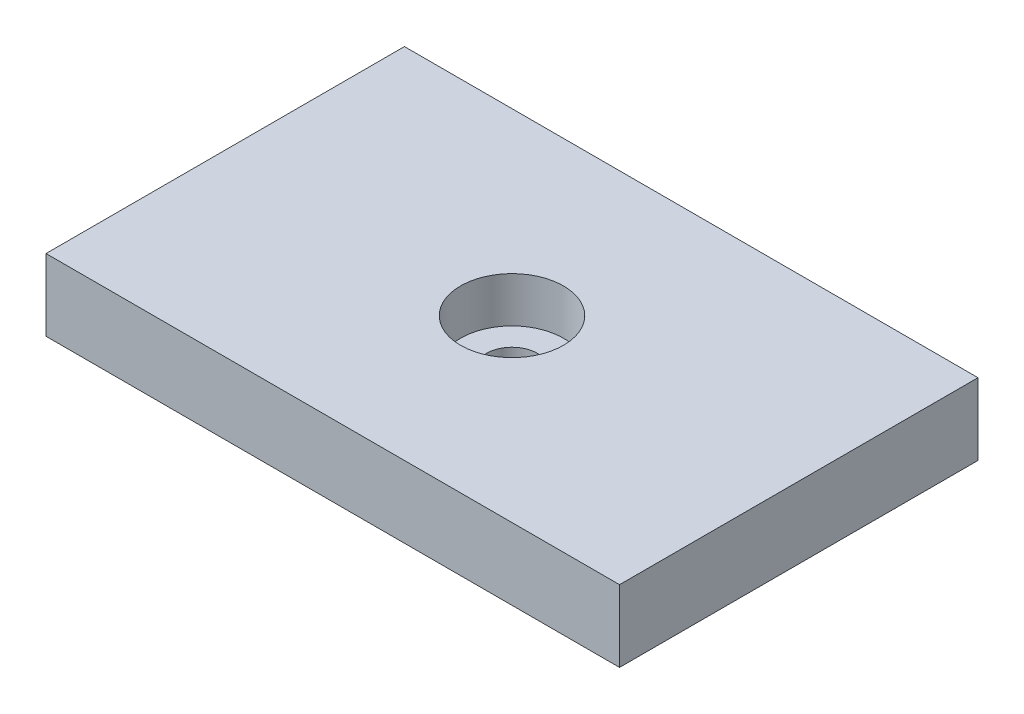
SolidWorks part; units mm, degrees
material "Silicon Rubber"
ref_plane "Front Plane" through (0, 0, 0) normal (0, 0, 1) x (1, 0, 0)
ref_plane "Top Plane" through (0, 0, 0) normal (0, 1, 0) x (1, 0, 0)
ref_plane "Right Plane" through (0, 0, 0) normal (1, 0, 0) x (0, 0, -1)
sketch "Sketch1" plane through (0, 0, 0) normal (0, 1, 0) x (1, 0, 0)
  line L0 (-25.4, 15.875) -> (25.4, 15.875)
  line L1 (-25.4, 15.875) -> (-25.4, -15.875)
  line L2 (25.4, 15.875) -> (25.4, -15.875)
  line L3 (-25.4, -15.875) -> (25.4, -15.875)
  line L4 (-25.4, 15.875) -> (25.4, -15.875) construction
  line L5 (25.4, 15.875) -> (-25.4, -15.875) construction
  circle A0 centre (0, 0) radius 2.2479
  circle A1 centre (0, 0) radius 4.5593
  dimension "D3" = 9.1186
  dimension "D4" = 4.4958
  dimension "D1" = 31.75
  dimension "D2" = 50.8
extrude "Boss-Extrude1" add sketch "Sketch1" along normal blind 6.35 contours L1 L3 L2 L0 A1 region at (0, 0, -15.2759)
extrude "Boss-Extrude2" add sketch "Sketch1<3>" along normal blind 2.3368 contours A1 A0 region at (-4.4303, 0, 0)
sketch "Sketch1<3>" plane through (0, 0, 0) normal (0, 1, 0) x (1, 0, 0) same geometry as "Sketch1"
